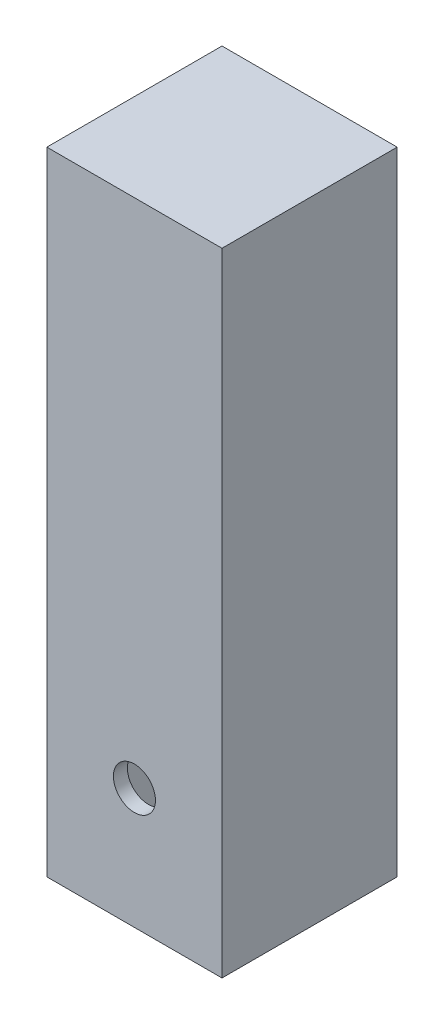
SolidWorks part; units mm, degrees
ref_plane "Front Plane" through (0, 0, 0) normal (0, 0, 1) x (1, 0, 0)
ref_plane "Top Plane" through (0, 0, 0) normal (0, 1, 0) x (1, 0, 0)
ref_plane "Right Plane" through (0, 0, 0) normal (1, 0, 0) x (0, 0, -1)
sketch "Sketch1" plane through (0, 0, 0) normal (0, 1, 0) x (1, 0, 0)
  line L0 (-12.5, 12.5) -> (12.5, -12.5) construction
  line L1 (-12.5, 12.5) -> (12.5, 12.5)
  line L2 (-12.5, 12.5) -> (-12.5, -12.5)
  line L3 (-12.5, -12.5) -> (12.5, -12.5)
  line L4 (12.5, 12.5) -> (12.5, -12.5)
  line L5 (-12.5, -12.5) -> (12.5, 12.5) construction
  dimension "D1" = 25
extrude "Boss-Extrude1" add sketch "Sketch1" along normal blind 120
shell "Shell1" thickness 2 removed face at (0, 0, 0)
hole_wizard "Ø6.0 (6) Diameter Hole1" positions "Sketch3" profile "Sketch2" hole size "Ø6.0" standard "ANSI Metric" end condition through all
sketch "Sketch3" plane through (0, 0, 12.5) normal (0, 0, 1) x (1, 0, 0)
  line L0 (-12.5, 0) -> (12.5, 0) construction
  line L1 (-12.5, 32) -> (12.5, 32) construction
  line L2 (-12.5, 120) -> (-12.5, 0) construction
  line L3 (12.5, 120) -> (12.5, 0) construction
  point P0 (0, 47)
  dimension "D1" = 47
  dimension "D2" = 15
sketch "Sketch2" plane through (0, 47, 12.5) normal (1, 0, 0) x (0, -1, 0)
  line L0 (0, 0) -> (0, 25)
  line L1 (0, 25) -> (3, 25)
  line L2 (3, 25) -> (3, 0)
  line L5 (3, 0) -> (0, 0)
  line L11 (0, -6.35) -> (0, 107.95) construction
  dimension "Thru Hole Dia." = 6
  dimension "Thru Hole Depth" = 25
sketch "Sketch4" plane through (0, 0, 12.5) normal (0, 0, 1) x (1, 0, 0)
  line L0 (-12.5, 31.4804) -> (12.5, 31.4804) construction
  line L1 (-12.5, 120) -> (-12.5, 0) construction
  line L2 (12.5, 120) -> (12.5, 0) construction
sketch "Sketch6" plane through (0, 0, 0) normal (0, 0, 1) x (1, 0, 0)
  line L1 (-16.1859, 29.7975) -> (19.0482, 29.7975)
  line L2 (-16.1859, 29.7975) -> (-16.1859, -11.1309)
  line L3 (-16.1859, -11.1309) -> (19.0482, -11.1309)
  line L4 (19.0482, 29.7975) -> (19.0482, -11.1309)
extrude "Cut-Extrude1" cut sketch "Sketch6" against normal blind 48.26
extrude "Cut-Extrude2" cut sketch "Sketch6<2>" against normal blind 48.26 and the other way blind 48.26
sketch "Sketch6<2>" plane through (0, 0, 0) normal (0, 0, 1) x (1, 0, 0) same geometry as "Sketch6"
